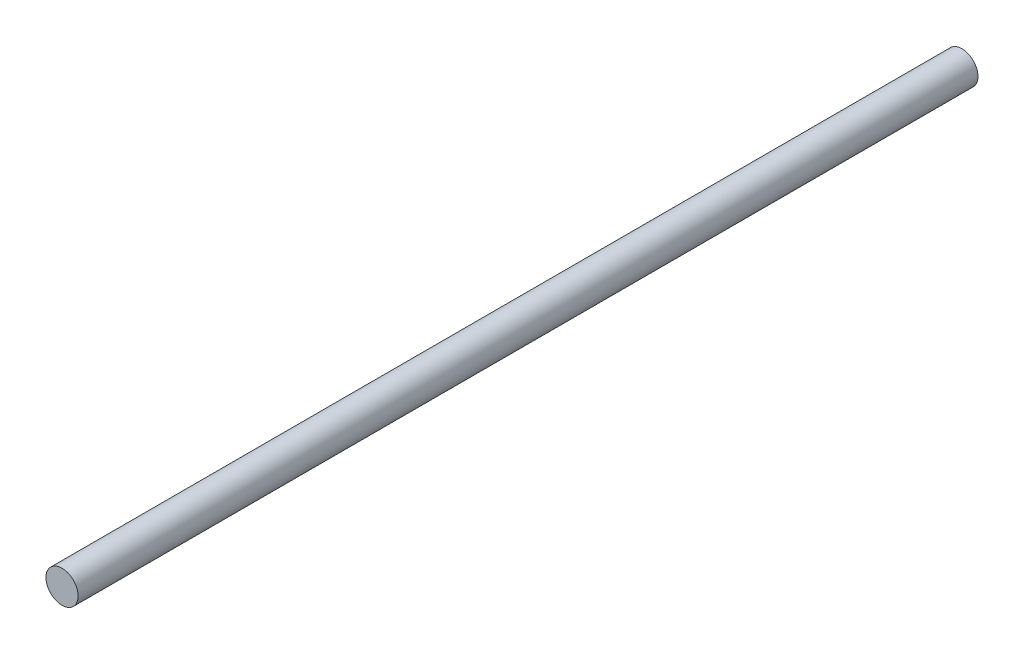
SolidWorks part; units mm, degrees
ref_plane "Front Plane" through (0, 0, 0) normal (0, 0, 1) x (1, 0, 0)
ref_plane "Top Plane" through (0, 0, 0) normal (0, 1, 0) x (1, 0, 0)
ref_plane "Right Plane" through (0, 0, 0) normal (1, 0, 0) x (0, 0, -1)
sketch "Sketch1" plane through (0, 0, 0) normal (0, 0, 1) x (1, 0, 0)
  circle A0 centre (0, 0) radius 1.5
extrude "Boss-Extrude1" add sketch "Sketch1" along normal blind 100
sketch "Sketch2" plane through (0, 0, 100) normal (0, 0, 1) x (1, 0, 0)
  circle A0 centre (0, 0) radius 1.5
extrude "Cut-Extrude1" cut sketch "Sketch2" against normal blind 16
ref_axis "Axis1" through (0, 0, 84) along (0, 0, -1)
